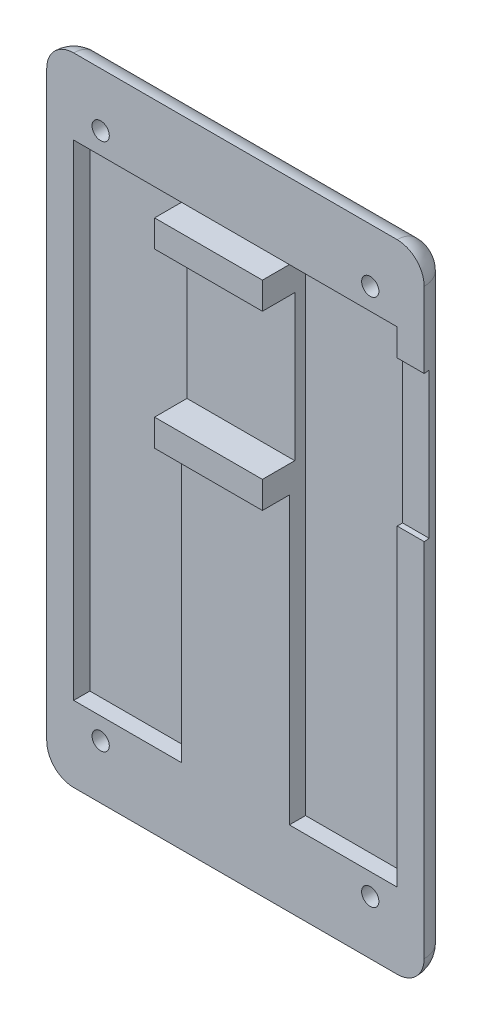
SolidWorks part; units mm, degrees
ref_plane "正面" through (0, 0, 0) normal (0, 0, 1) x (1, 0, 0)
ref_plane "平面" through (0, 0, 0) normal (0, 1, 0) x (1, 0, 0)
ref_plane "右側面" through (0, 0, 0) normal (1, 0, 0) x (0, 0, -1)
sketch "ｽｹｯﾁ1" plane through (0, 0, 0) normal (0, 0, 1) x (1, 0, 0)
  line L1 (-35, -59) -> (35, -59)
  line L2 (-35, -59) -> (-35, 59)
  line L3 (-35, 59) -> (35, 59)
  line L4 (35, -59) -> (35, 59)
  line L5 (-35, -59) -> (35, 59) construction
  line L6 (-35, 59) -> (35, -59) construction
  point P0 (0, 0)
  dimension "D1" = 118
  dimension "D2" = 70
extrude "ﾎﾞｽ - 押し出し1" add sketch "ｽｹｯﾁ1" along normal blind 40
sketch "ｽｹｯﾁ2" plane through (0, 0, 40) normal (0, 0, 1) x (1, 0, 0)
  line L1 (-32, -56) -> (32, -56)
  line L2 (-32, -56) -> (-32, 56)
  line L3 (-32, 56) -> (32, 56)
  line L4 (32, -56) -> (32, 56)
  line L5 (-32, -56) -> (32, 56) construction
  line L6 (-32, 56) -> (32, -56) construction
  point P0 (0, 0)
  dimension "D1" = 112
  dimension "D2" = 64
extrude "ｶｯﾄ - 押し出し1" cut sketch "ｽｹｯﾁ2" against normal blind 35
sketch "ｽｹｯﾁ3" plane through (0, 0, 5) normal (0, 0, 1) x (1, 0, 0)
  line L1 (-25, -49) -> (25, -49) construction
  line L2 (-25, -49) -> (-25, 49) construction
  line L3 (-25, 49) -> (25, 49) construction
  line L4 (25, -49) -> (25, 49) construction
  line L5 (-25, -49) -> (25, 49) construction
  line L6 (-25, 49) -> (25, -49) construction
  circle A0 centre (-25, 49) radius 1.6
  circle A1 centre (25, 49) radius 1.6
  circle A2 centre (-25, -49) radius 1.6
  circle A3 centre (25, -49) radius 1.6
  point P0 (0, 0)
  dimension "D1" = 50
  dimension "D2" = 98
  dimension "D3" = 3.2
  dimension "D4" = 3.2
  dimension "D5" = 3.2
  dimension "D6" = 3.2
extrude "ｶｯﾄ - 押し出し2" cut sketch "ｽｹｯﾁ3" against normal through all
fillet "ﾌｨﾚｯﾄ1" radius 5 4 edges at (0, -59, 0) (0, 59, 0) (-35, 0, 0) (35, 0, 0)
fillet "ﾌｨﾚｯﾄ2" radius 5 8 edges at (-33.5355, 57.5355, 1.4645) (-33.5355, -57.5355, 1.4645) (33.5355, 57.5355, 1.4645) (33.5355, -57.5355, 1.4645) (-35, 59, 22.5) (-35, -59, 22.5) (35, 59, 22.5) (35, -59, 22.5)
sketch "ｽｹｯﾁ4" plane through (0, 0, 40) normal (0, 0, 1) x (1, 0, 0)
  line L1 (40, 60) -> (-40, 60)
  line L2 (40, 60) -> (40, -60)
  line L3 (40, -60) -> (-40, -60)
  line L4 (-40, 60) -> (-40, -60)
  line L5 (40, 60) -> (-40, -60) construction
  line L6 (40, -60) -> (-40, 60) construction
  point P0 (0, 0)
  dimension "D1" = 120
  dimension "D2" = 80
extrude "ｶｯﾄ - 押し出し3" cut sketch "ｽｹｯﾁ4" against normal blind 35
sketch "ｽｹｯﾁ5" plane through (0, 0, 5) normal (0, 0, 1) x (1, 0, 0)
  line L0 (35, -54) -> (35, 54) construction
  line L1 (35, 13) -> (-25, 13)
  line L2 (35, 13) -> (35, 40)
  line L3 (35, 40) -> (-25, 40)
  line L4 (-25, 13) -> (-25, 40)
  line L5 (30, 59) -> (-30, 59) construction
  dimension "D1" = 27
  dimension "D2" = 60
  dimension "D3" = 19
extrude "ｶｯﾄ - 押し出し4" cut sketch "ｽｹｯﾁ5" against normal blind 1
sketch "ｽｹｯﾁ6" plane through (0, 0, 5) normal (0, 0, 1) x (1, 0, 0)
  line L0 (-35, 54) -> (-35, -54) construction
  line L1 (-30, -45) -> (-10, -45)
  line L2 (-30, -45) -> (-30, 45)
  line L3 (-30, 45) -> (-10, 45)
  line L4 (-10, -45) -> (-10, 45)
  point P6 (-35, 0)
  point P7 (-30, 0)
  dimension "D1" = 90
  dimension "D2" = 0
  dimension "D3" = 20
  dimension "D4" = 5
extrude "ｶｯﾄ - 押し出し5" cut sketch "ｽｹｯﾁ6" against normal blind 3
sketch "ｽｹｯﾁ7" plane through (0, 0, 5) normal (0, 0, 1) x (1, 0, 0)
  line L0 (35, -54) -> (35, 13) construction
  line L1 (10, -45) -> (30, -45)
  line L2 (10, -45) -> (10, 45)
  line L3 (10, 45) -> (30, 45)
  line L4 (30, -45) -> (30, 45)
  point P6 (30, 0)
  dimension "D1" = 5
  dimension "D2" = 20
  dimension "D3" = 90
  dimension "D4" = 0
extrude "ｶｯﾄ - 押し出し6" cut sketch "ｽｹｯﾁ7" against normal blind 3
sketch "ｽｹｯﾁ8" plane through (0, 0, 5) normal (0, 0, 1) x (1, 0, 0)
  line L0 (10, 45) -> (10, -45) construction
  line L1 (-10, 13) -> (10, 13)
  line L2 (-10, 13) -> (-10, 8)
  line L3 (-10, 8) -> (10, 8)
  line L4 (10, 13) -> (10, 8)
  line L6 (-10, 40) -> (10, 40)
  line L7 (-10, 40) -> (-10, 45)
  line L8 (-10, 45) -> (10, 45)
  line L9 (10, 40) -> (10, 45)
  dimension "D1" = 5
extrude "ﾎﾞｽ - 押し出し2" add sketch "ｽｹｯﾁ8" along normal blind 5
